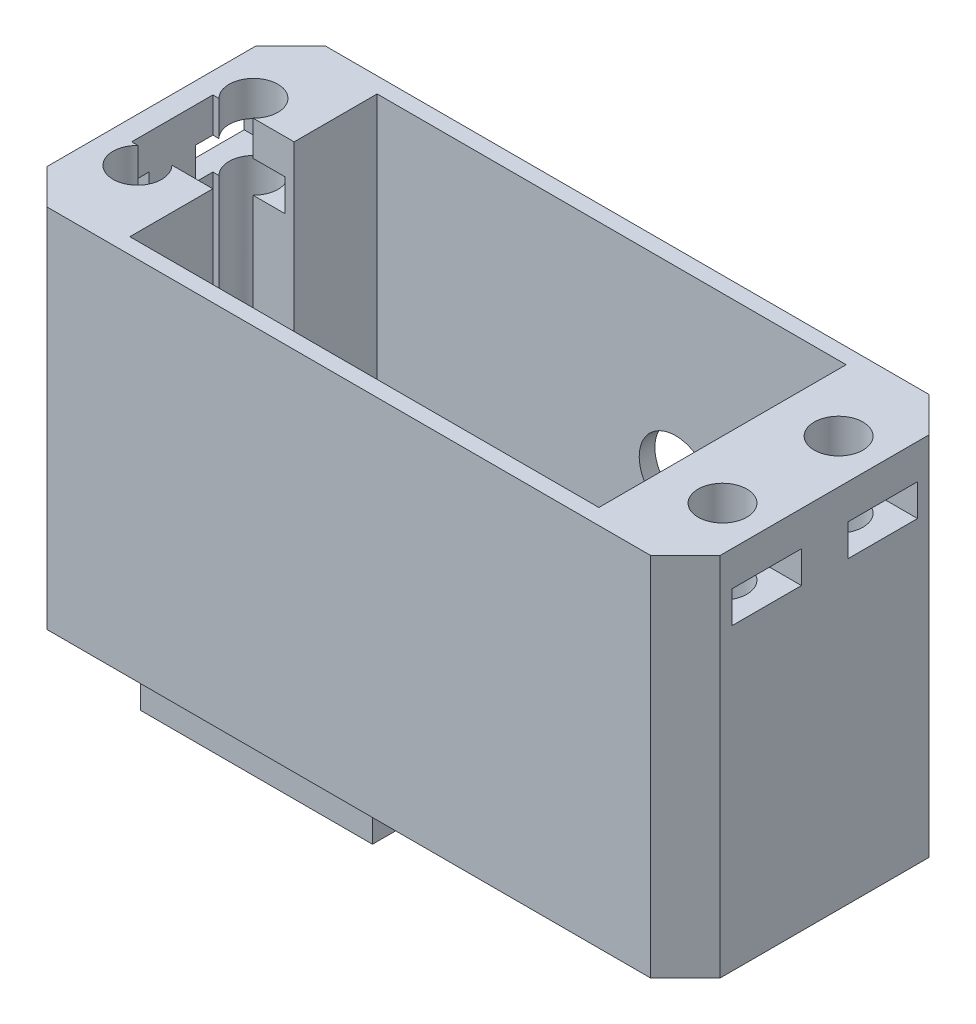
SolidWorks part; units mm, degrees
ref_plane "Front Plane" through (0, 0, 0) normal (0, 0, 1) x (1, 0, 0)
ref_plane "Top Plane" through (0, 0, 0) normal (0, 1, 0) x (1, 0, 0)
ref_plane "Right Plane" through (0, 0, 0) normal (1, 0, 0) x (0, 0, -1)
sketch "Sketch1" plane through (0, 0, 0) normal (0, 1, 0) x (1, 0, 0)
  line L0 (9.75, 1.0273) -> (50.15, 1.0273)
  line L1 (50.15, 1.0273) -> (50.15, -20.2727)
  line L2 (50.15, -20.2727) -> (9.75, -20.2727)
  line L4 (0.95, -21.6227) -> (58.95, -21.6227)
  line L5 (58.95, -21.6227) -> (58.95, 2.3773)
  line L6 (58.95, 2.3773) -> (0.95, 2.3773)
  line L8 (55.15, -4.6227) -> (55.15, -14.6227) construction
  line L9 (0.95, 2.3773) -> (0.95, -21.6227)
  line L10 (9.75, 1.0273) -> (9.75, -20.2727)
  line L11 (29.95, 1.0273) -> (29.95, -20.2727) construction
  circle A0 centre (55.15, -4.6227) radius 2.1
  circle A1 centre (55.15, -14.6227) radius 2.1
  circle A2 centre (4.75, -14.6227) radius 2.1
  circle A3 centre (4.75, -4.6227) radius 2.1
  point P13 (55.15, -9.6227)
  point P14 (50.15, -9.6227)
  point P20 (0.95, -9.6227)
  point P22 (29.95, 2.3773)
  dimension "D1" = 4.2
  dimension "D2" = 10
  dimension "D3" = 24
  dimension "D4" = 40.4
  dimension "D5" = 5
  dimension "D6" = 21.3
  dimension "D7" = 58
extrude "Boss-Extrude1" add sketch "Sketch1" along normal blind 28.35
sketch "Sketch11" plane through (0, 0, 0) normal (0, -1, 0) x (1, 0, 0)
  line L1 (0.95, 21.6227) -> (58.95, 21.6227)
  line L2 (0.95, 21.6227) -> (0.95, -2.3773)
  line L3 (0.95, -2.3773) -> (58.95, -2.3773)
  line L4 (58.95, 21.6227) -> (58.95, -2.3773)
extrude "Boss-Extrude5" add sketch "Sketch11" along normal blind 3.175
sketch "Sketch14" plane through (0, 0, -2.3773) normal (0, 0, -1) x (-1, 0, 0)
  line L0 (-0.95, 28.35) -> (-0.95, -3.175) construction
  line L8 (-0.95, 6.5875) -> (-24.95, 6.5875)
  line L9 (-0.95, 6.5875) -> (-0.95, 18.5875)
  line L10 (-0.95, 18.5875) -> (-24.95, 18.5875)
  line L11 (-24.95, 6.5875) -> (-24.95, 18.5875)
  line L12 (-0.95, 6.5875) -> (-24.95, 18.5875) construction
  line L13 (-0.95, 18.5875) -> (-24.95, 6.5875) construction
  point P0 (-12.95, 12.5875)
  point P5 (-12.95, 12.5875)
  point P6 (-0.95, 12.5875)
  dimension "D1" = 24
  dimension "D2" = 12
  dimension "D3" = 0
extrude "Boss-Extrude7" add sketch "Sketch14" along normal blind 9
ref_plane "Plane1" through (0, 0, -6.8773) normal (0, 0, -1) x (-1, 0, 0)
sketch "Sketch16" plane through (0, 0, -6.8773) normal (0, 0, -1) x (-1, 0, 0)
  line L1 (-11.45, 16.7875) -> (-24.95, 16.7875)
  line L3 (-11.45, 8.3875) -> (-24.95, 8.3875)
  line L4 (-24.95, 16.7875) -> (-24.95, 8.3875)
  line L6 (-24.95, 18.5875) -> (-24.95, 6.5875) construction
  arc A0 (-11.45, 8.3875) -> (-11.45, 16.7875) centre (-11.45, 12.5875) ccw
  point P10 (-24.95, 12.5875)
  dimension "D2" = 4.2
  dimension "D1" = 13.5
extrude "Cut-Extrude1" cut sketch "Sketch16" along normal blind 7.6 from surface starting at face at (21.45, 12.5875, -2.3773)
fillet "Fillet1" radius 8 2 edges at (12.95, 6.5875, -2.3773) (12.95, 18.5875, -2.3773)
chamfer "Chamfer2" distance 3 angle 45 9 edges at (0.95, 27.4688, -2.3773) (0.95, -2.2938, -2.3773) (0.95, 12.5875, 21.6227) (58.95, 12.5875, 21.6227) (0.95, 18.5875, -10.8773) (0.95, 20.9306, -4.7205) (0.95, 6.5875, -10.8773) (0.95, 4.2444, -4.7205) (58.95, 12.5875, -2.3773)
chamfer "Chamfer3" distance 1 angle 45 4 edges at (24.95, 12.5875, -11.3773) (14.45, 6.5875, -11.3773) (0.95, 12.5875, -11.3773) (14.45, 18.5875, -11.3773)
ref_plane "Plane2" through (0, 25.35, 0) normal (0, 1, 0) x (1, 0, 0)
sketch "Sketch19" plane through (0, 25.35, 0) normal (0, 1, 0) x (1, 0, 0)
  line L0 (0.95, -0.6227) -> (0.95, -18.6227) construction
  line L1 (0.95, -1.6227) -> (8.95, -1.6227)
  line L2 (0.95, -1.6227) -> (0.95, -7.6227)
  line L3 (0.95, -7.6227) -> (8.95, -7.6227)
  line L4 (8.95, -1.6227) -> (8.95, -7.6227)
  line L5 (-0.5892, -9.6227) -> (60.8708, -9.6227) construction
  line L6 (29.95, -22.0073) -> (29.95, 3.0189) construction
  line L7 (9.75, 1.0273) -> (9.75, -20.2727) construction
  line L8 (50.15, 1.0273) -> (9.75, 1.0273) construction
  line L9 (8.95, -17.6227) -> (8.95, -11.6227)
  line L10 (0.95, -11.6227) -> (8.95, -11.6227)
  line L11 (0.95, -17.6227) -> (0.95, -11.6227)
  line L12 (0.95, -17.6227) -> (8.95, -17.6227)
  line L37 (60.4892, -9.6227) -> (-0.9708, -9.6227) construction
  line L38 (58.95, -17.6227) -> (50.95, -17.6227)
  line L39 (58.95, -17.6227) -> (58.95, -11.6227)
  line L40 (58.95, -11.6227) -> (50.95, -11.6227)
  line L41 (50.95, -17.6227) -> (50.95, -11.6227)
  line L42 (50.95, -1.6227) -> (50.95, -7.6227)
  line L43 (58.95, -7.6227) -> (50.95, -7.6227)
  line L44 (58.95, -1.6227) -> (58.95, -7.6227)
  line L45 (58.95, -1.6227) -> (50.95, -1.6227)
  circle A0 centre (4.75, -4.6227) radius 2.1 construction
  circle A1 centre (4.75, -4.6227) radius 2.1 construction
  circle A2 centre (4.75, -14.6227) radius 2.1 construction
  circle A3 centre (4.75, -4.6227) radius 2.1 construction
  circle A4 centre (4.75, -14.6227) radius 2.1 construction
  circle A5 centre (4.75, -4.6227) radius 2.1 construction
  circle A6 centre (4.75, -14.6227) radius 2.1 construction
  circle A7 centre (4.75, -4.6227) radius 2.1 construction
  circle A8 centre (4.75, -14.6227) radius 2.1 construction
  circle A9 centre (55.15, -14.6227) radius 2.1 construction
  circle A10 centre (55.15, -4.6227) radius 2.1 construction
  circle A11 centre (55.15, -14.6227) radius 2.1 construction
  circle A12 centre (55.15, -4.6227) radius 2.1 construction
  circle A13 centre (55.15, -14.6227) radius 2.1 construction
  circle A14 centre (55.15, -4.6227) radius 2.1 construction
  circle A15 centre (55.15, -14.6227) radius 2.1 construction
  circle A16 centre (55.15, -4.6227) radius 2.1 construction
  point P11 (0.95, -4.6227)
  point P18 (9.75, -9.6227)
  point P21 (29.95, 1.0273)
  point P28 (0.95, -14.6227)
  point P55 (58.95, -14.6227)
  point P56 (58.95, -4.6227)
  dimension "D1" = 6
  dimension "D2" = 8
extrude "Cut-Extrude3" cut sketch "Sketch19" against normal blind 2.75
sketch "Sketch20" plane through (0, 0, 0) normal (0, 1, 0) x (1, 0, 0)
  line L0 (0.95, -0.6227) -> (0.95, -18.6227) construction
  line L1 (0.95, -13.8727) -> (9.75, -13.8727)
  line L2 (0.95, -13.8727) -> (0.95, -5.3727)
  line L3 (0.95, -5.3727) -> (9.75, -5.3727)
  line L4 (9.75, -13.8727) -> (9.75, -5.3727)
  line L5 (9.75, 1.0273) -> (9.75, -20.2727) construction
  point P6 (0.95, -9.6227)
  dimension "D1" = 8.5
extrude "Cut-Extrude4" cut sketch "Sketch20" along normal blind 4
sketch "Sketch21" plane through (0, -3.175, 0) normal (0, -1, 0) x (1, 0, 0)
  line L0 (0.95, 18.6227) -> (0.95, 0.6227) construction
  line L1 (30, -0.3773) -> (10, -0.3773)
  line L2 (30, -0.3773) -> (30, 19.6227)
  line L3 (30, 19.6227) -> (10, 19.6227)
  line L4 (10, -0.3773) -> (10, 19.6227)
  line L5 (30, -0.3773) -> (10, 19.6227) construction
  line L6 (30, 19.6227) -> (10, -0.3773) construction
  point P0 (20, 9.6227)
  point P7 (0.95, 9.6227)
  dimension "D1" = 19.05
  dimension "D2" = 20
  dimension "D3" = 20
extrude "Boss-Extrude8" add sketch "Sketch21" along normal blind 6
sketch "Sketch13" plane through (0, -9.175, 0) normal (0, -1, 0) x (1, 0, 0)
  line L0 (0.95, 18.6227) -> (0.95, 0.6227) construction
  circle A0 centre (20, 9.6227) radius 2.55
  point P2 (0.95, 9.6227)
  dimension "D2" = 5.1
  dimension "D1" = 19.05
extrude "Boss-Extrude6" add sketch "Sketch13" along normal blind 5
fillet "Fillet4" radius 1 4 edges at (20, -3.175, 19.6227) (30, -3.175, 9.6227) (20, -3.175, -0.3773) (10, -3.175, 9.6227)
chamfer "Chamfer4" distance 2 angle 45 4 edges at (20, -9.175, 19.6227) (30, -9.175, 9.6227) (20, -9.175, -0.3773) (10, -9.175, 9.6227)
fillet "Fillet5" radius 1 1 edges at (20, -14.175, 7.0727)
sketch "Sketch22" plane through (0, 28.35, 0) normal (0, 1, 0) x (1, 0, 0)
  line L0 (9.75, 1.0273) -> (9.75, -20.2727) construction
  line L2 (9.75, -6.1227) -> (2.75, -6.1227)
  line L3 (9.75, -6.1227) -> (9.75, -13.1227)
  line L4 (9.75, -13.1227) -> (2.75, -13.1227)
  line L5 (2.75, -6.1227) -> (2.75, -13.1227)
  point P0 (9.75, -9.6227)
  dimension "D1" = 7
  dimension "D2" = 7
extrude "Cut-Extrude5" cut sketch "Sketch22" against normal up to surface (28.35 mm away) up to face at (13.35, 0, 9.6227)
sketch "Sketch23" plane through (0, 0, -11.3773) normal (0, 0, -1) x (-1, 0, 0)
  arc A0 (-10.2, 12.5875) -> (-12.7, 12.5875) centre (-11.45, 12.5875) ccw construction
  arc A1 (-12.7, 12.5875) -> (-10.2, 12.5875) centre (-11.45, 12.5875) ccw construction
  arc A2 (-14.2, 12.5875) -> (-16.7, 12.5875) centre (-15.45, 12.5875) ccw construction
  arc A3 (-16.7, 12.5875) -> (-14.2, 12.5875) centre (-15.45, 12.5875) ccw construction
  arc A4 (-10.2, 12.5875) -> (-12.7, 12.5875) centre (-11.45, 12.5875) ccw
  arc A5 (-12.7, 12.5875) -> (-10.2, 12.5875) centre (-11.45, 12.5875) ccw
  arc A6 (-14.2, 12.5875) -> (-16.7, 12.5875) centre (-15.45, 12.5875) ccw
  arc A7 (-16.7, 12.5875) -> (-14.2, 12.5875) centre (-15.45, 12.5875) ccw
extrude "Cut-Extrude6" cut sketch "Sketch23" against normal up to surface (1.4 mm away) up to face at (17.15, 12.5875, -9.9773)
sketch "Sketch24" plane through (0, 0, -2.3773) normal (0, 0, -1) x (-1, 0, 0)
  circle A0 centre (-35.45, 12.5875) radius 3.125
  dimension "D1" = 6.25
extrude "Cut-Extrude7" cut sketch "Sketch24" against normal up to surface (1.35 mm away) up to face at (29.95, 14.175, -1.0273)
